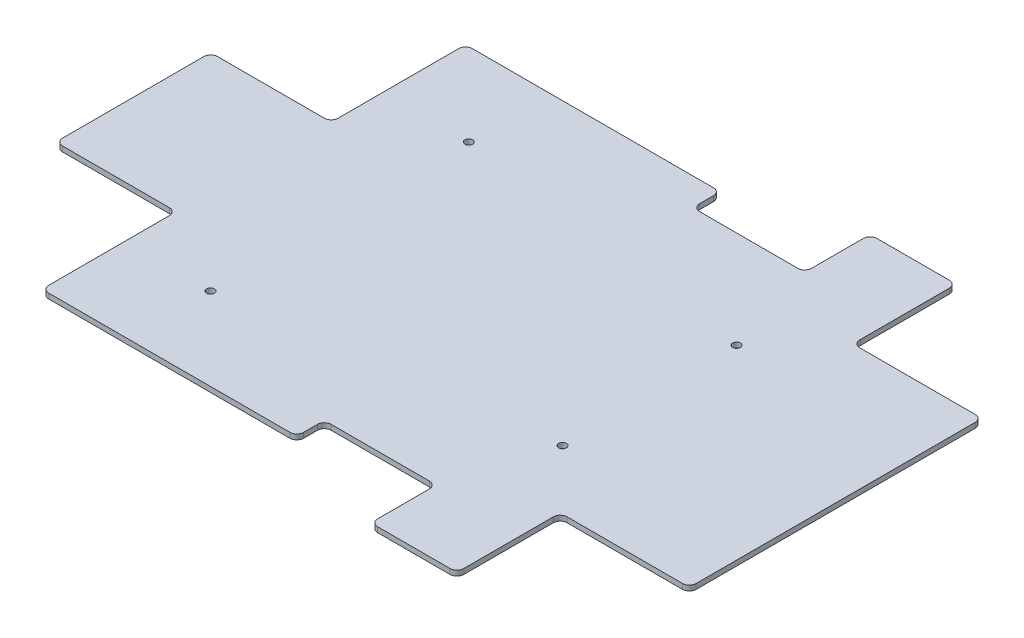
SolidWorks part; units mm, degrees
material "Aleación 1060"
ref_plane "Alzado" through (0, 0, 0) normal (0, 0, 1) x (1, 0, 0)
ref_plane "Planta" through (0, 0, 0) normal (0, 1, 0) x (1, 0, 0)
ref_plane "Vista lateral" through (0, 0, 0) normal (1, 0, 0) x (0, 0, -1)
sketch "Croquis1" plane through (0, 0, 0) normal (0, 1, 0) x (1, 0, 0)
  line L0 (0, 0) -> (-408, 0)
  line L1 (-408, 0) -> (-408, 45)
  line L2 (-408, 45) -> (-338, 45)
  line L3 (-338, 45) -> (-338, 123)
  line L4 (-338, 123) -> (-190, 123)
  line L5 (-190, 123) -> (-190, 107)
  line L6 (-190, 107) -> (-125, 107)
  line L7 (-125, 107) -> (-125, 145)
  line L8 (-125, 145) -> (-75, 145)
  line L9 (-75, 145) -> (-75, 85)
  line L10 (0, 0) -> (0, 85)
  line L11 (0, 85) -> (-75, 85)
  dimension "D1" = 408
  dimension "D2" = 45
  dimension "D3" = 75
  dimension "D4" = 123
  dimension "D5" = 148
  dimension "D6" = 16
  dimension "D7" = 50
  dimension "D8" = 85
  dimension "D9" = 65
  dimension "D10" = 60
extrude "Saliente-Extruir1" add sketch "Croquis1" along normal blind 3
mirror "Simetría1" about plane through (0, 3, 0) normal (0, 0, -1) of "Saliente-Extruir1"
fillet "Redondeo1" radius 4 20 edges at (-408, 1.5, -45) (-338, 1.5, -45) (-338, 1.5, -123) (-190, 1.5, -123) (-190, 1.5, -107) (-125, 1.5, -107) (-125, 1.5, -145) (-75, 1.5, -85) (-75, 1.5, -145) (0, 1.5, -85) (0, 1.5, 85) (-75, 1.5, 85) (-75, 1.5, 145) (-125, 1.5, 145) (-125, 1.5, 107) (-190, 1.5, 107) (-190, 1.5, 123) (-338, 1.5, 123) (-338, 1.5, 45) (-408, 1.5, 45)
sketch "Croquis2" plane through (0, 3, 0) normal (0, 1, 0) x (1, 0, 0)
  line L0 (-408, 0) -> (0, 0) construction
  line L1 (-408, 41) -> (-408, -41) construction
  line L2 (0, -81) -> (0, 81) construction
  line L3 (-214.7209, -131) -> (31.1095, -131) construction
  line L4 (-214.0485, -154) -> (44.3152, -154) construction
  line L5 (-79, -145) -> (-121, -145) construction
  line L6 (-44, -177) -> (-156, -177)
  line L7 (-44, -177) -> (-44, -131)
  line L8 (-44, -131) -> (-156, -131)
  line L9 (-156, -177) -> (-156, -131)
  line L10 (-44, -177) -> (-156, -131) construction
  line L11 (-44, -131) -> (-156, -177) construction
  line L12 (-156, 154) -> (-44, 154) construction
  line L13 (-374, -177) -> (-486, -177)
  line L14 (-374, -177) -> (-374, -131)
  line L15 (-374, -131) -> (-486, -131)
  line L16 (-486, -177) -> (-486, -131)
  line L17 (-374, -177) -> (-486, -131) construction
  line L18 (-374, -131) -> (-486, -177) construction
  line L19 (-44, 177) -> (-156, 177)
  line L20 (-44, 177) -> (-44, 131)
  line L21 (-44, 131) -> (-156, 131)
  line L22 (-156, 177) -> (-156, 131)
  line L23 (-374, 131) -> (-486, 177) construction
  line L24 (-374, 177) -> (-486, 131) construction
  line L25 (-486, 177) -> (-486, 131)
  line L26 (-374, 131) -> (-486, 131)
  line L27 (-374, 177) -> (-374, 131)
  line L28 (-374, 177) -> (-486, 177)
  line L29 (-430, -154) -> (-430, 154) construction
  point P10 (-100, -154)
  point P17 (-100, -145)
  point P20 (-430, -154)
  point P33 (-430, 154)
  dimension "D1" = 131
  dimension "D2" = 154
  dimension "D3" = 46
  dimension "D4" = 112
  dimension "D5" = 330
  dimension "D6" = 308
sketch "Croquis3" plane through (0, 3, 0) normal (0, 1, 0) x (1, 0, 0)
  line L0 (-100, -145) -> (-100, 145) construction
  line L1 (-79, -145) -> (-121, -145) construction
  line L2 (-79, 145) -> (-121, 145) construction
  line L3 (-161.61, 16.8885) -> (-161.61, -25.475) construction
  line L4 (-232.2, 27.5722) -> (-232.2, -25.475) construction
  dimension "D1" = 132.2
  dimension "D2" = 61.61
ref_plane "Plano1" [suppressed] through (-430, 0, 0) normal (1, 0, 0) x (0, 0, -1)
sketch "Croquis4" plane through (0, 3, 0) normal (0, 1, 0) x (1, 0, 0)
  circle A0 centre (-108.1, -50.5) radius 2.25
  dimension "D1" = 4.5
extrude "Cortar-Extruir1" cut sketch "Croquis4" against normal blind 10
mirror "Simetría2" about plane through (0, 0, 0) normal (0, 0, 1) of "Cortar-Extruir1"
sketch "Croquis5" plane through (0, 3, 0) normal (0, 1, 0) x (1, 0, 0)
  circle A0 centre (-288.1, -75) radius 2.25
  dimension "D1" = 4.5
extrude "Cortar-Extruir2" cut sketch "Croquis5" against normal blind 10
mirror "Simetría3" about plane through (0, 0, 0) normal (0, 0, 1) of "Cortar-Extruir2"
